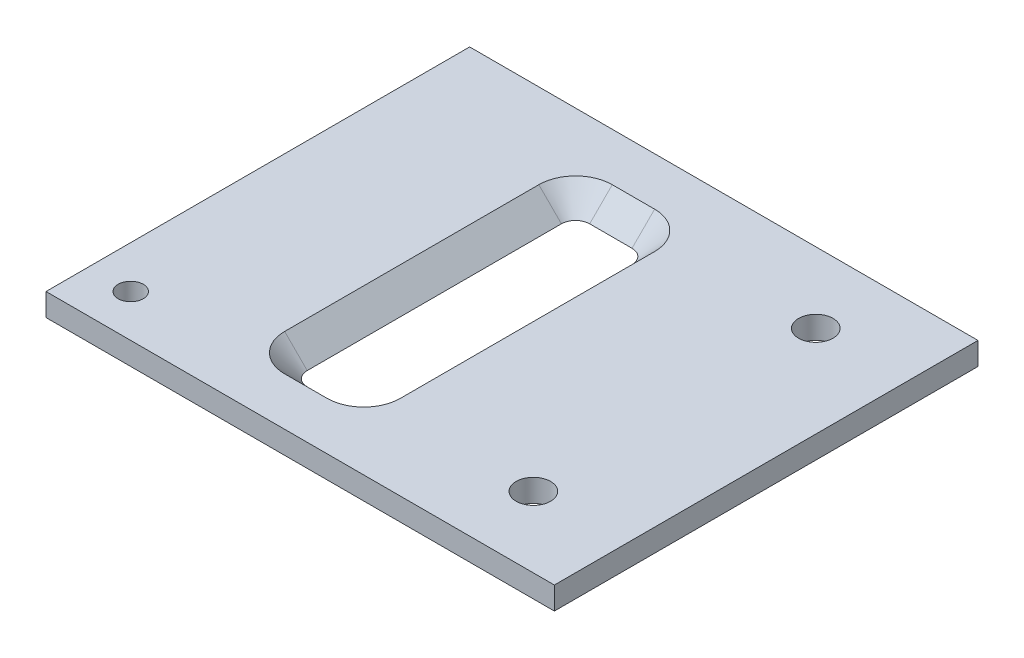
SolidWorks part; units mm, degrees
material "6061-T4 (SS)"
ref_plane "Front Plane" through (0, 0, 0) normal (0, 0, 1) x (1, 0, 0)
ref_plane "Top Plane" through (0, 0, 0) normal (0, 1, 0) x (1, 0, 0)
ref_plane "Right Plane" through (0, 0, 0) normal (1, 0, 0) x (0, 0, -1)
sketch "Sketch2" plane through (0, 0, 0) normal (0, 1, 0) x (1, 0, 0)
  line L0 (3, 0) -> (0, 0) construction
  line L5 (-15, 15) -> (21, 15)
  line L6 (-15, 15) -> (-15, -15)
  line L7 (-15, -15) -> (21, -15)
  line L8 (21, 15) -> (21, -15)
  line L9 (-15, 15) -> (21, -15) construction
  line L10 (-15, -15) -> (21, 15) construction
  dimension "D1" = 36
  dimension "D2" = 30
  dimension "D3" = 3
extrude "Boss-Extrude1" add sketch "Sketch2" along normal blind 1.6002
sketch "Sketch4" plane through (0, 0, 0) normal (0, 1, 0) x (1, 0, 0)
  line L1 (1.5, -10) -> (-1.5, -10)
  line L2 (2.5, -9) -> (2.5, 9)
  line L3 (1.5, 10) -> (-1.5, 10)
  line L4 (-2.5, -9) -> (-2.5, 9)
  line L5 (2.5, -10) -> (-2.5, 10) construction
  line L6 (2.5, 10) -> (-2.5, -10) construction
  arc A0 (1.5, -10) -> (2.5, -9) centre (1.5, -9) ccw
  arc A1 (2.5, 9) -> (1.5, 10) centre (1.5, 9) ccw
  arc A2 (-1.5, 10) -> (-2.5, 9) centre (-1.5, 9) ccw
  arc A3 (-1.5, -10) -> (-2.5, -9) centre (-1.5, -9) cw
  point P0 (0, 0)
  dimension "D3" = 1
  dimension "D1" = 20
  dimension "D2" = 5
extrude "Cut-Extrude4" cut sketch "Sketch4" along normal through all draft 45 draft outward yes
sketch3d "3DSketch1"
  line L0 (0, 2, 0) -> (0, 20.7837, 0) construction
hole_wizard "#2 Clearance Hole1" positions "Sketch7" profile "Sketch6" hole size "#2" standard "ANSI Inch" end condition through all
sketch "Sketch7" plane through (0, 0, 0) normal (0, -1, 0) x (-1, 0, 0)
  circle A0 centre (-14.5138, 10) radius 0.889 construction
  circle A1 centre (-14.5138, -10) radius 0.889 construction
  point P0 (-14.5138, -10)
  point P2 (-14.5138, 10)
sketch "Sketch6" plane through (14.5138, 0, 10) normal (1, 0, 0) x (0, 0, -1)
  line L0 (0, 0) -> (0, 1.6002)
  line L1 (0, 1.6002) -> (1.2192, 1.6002)
  line L2 (1.2192, 1.6002) -> (1.2192, 0)
  line L5 (1.2192, 0) -> (0, 0)
  line L11 (0, -6.35) -> (0, 107.95) construction
  dimension "Thru Hole Dia." = 2.4384
  dimension "Thru Hole Depth" = 1.6002
hole_wizard "#0 Clearance Hole1" positions "Sketch8" profile "Sketch10" hole size "#0" standard "ANSI Inch" end condition through all
sketch "Sketch8" plane through (0, 0, 0) normal (0, -1, 0) x (-1, 0, 0)
  line L1 (12, -12) -> (12, 0) construction
  line L5 (15, 15) -> (15, -15) construction
  line L7 (12, 0) -> (15, 0) construction
  line L9 (15, -15) -> (-21, -15) construction
  point P0 (12, -12)
  point P28 (15, 0)
  point P29 (12.8393, -12.9163)
  dimension "D1" = 3
  dimension "D2" = 3
sketch "Sketch10" plane through (-12, 0, 12) normal (1, 0, 0) x (0, 0, -1)
  line L0 (0, 0) -> (0, 1.6002)
  line L1 (0, 1.6002) -> (0.889, 1.6002)
  line L2 (0.889, 1.6002) -> (0.889, 0)
  line L5 (0.889, 0) -> (0, 0)
  line L11 (0, -6.35) -> (0, 107.95) construction
  dimension "Thru Hole Dia." = 1.778
  dimension "Thru Hole Depth" = 1.6002
